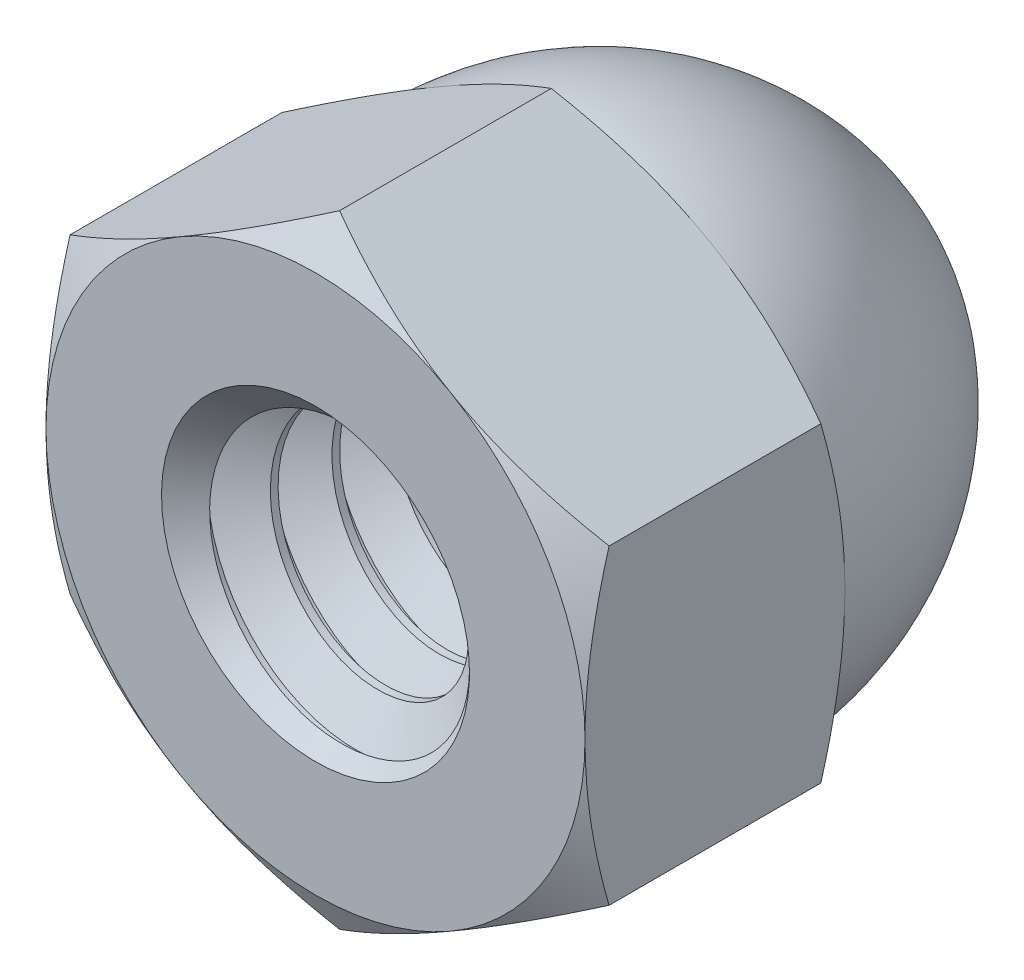
SolidWorks part; units mm, degrees
ref_plane "Front Plane" through (0, 0, 0) normal (0, 0, 1) x (1, 0, 0)
ref_plane "Top Plane" through (0, 0, 0) normal (0, 1, 0) x (1, 0, 0)
ref_plane "Right Plane" through (0, 0, 0) normal (1, 0, 0) x (0, 0, -1)
sketch "Sketch1" plane through (0, 0, 0) normal (0, 0, 1) x (1, 0, 0)
  line L1 (0, 6.4158) -> (-5.5563, 3.2079)
  line L2 (-5.5563, 3.2079) -> (-5.5563, -3.2079)
  line L3 (-5.5563, -3.2079) -> (0, -6.4158)
  line L4 (0, -6.4158) -> (5.5562, -3.2079)
  line L5 (5.5562, -3.2079) -> (5.5562, 3.2079)
  line L6 (5.5562, 3.2079) -> (0, 6.4158)
  circle A0 centre (0, 0) radius 5.5563 construction
  dimension "Hex" = 11.1125
extrude "Extrude1" add sketch "Sketch1" against normal blind 5.3578
sketch "Sketch2" plane through (0, 0, 0) normal (0, 0, 1) x (1, 0, 0)
  circle A0 centre (0, 0) radius 5.5563 construction
  circle A1 centre (0, 0) radius 5.5563
extrude "Cut-Extrude1" cut sketch "Sketch2" against normal through all draft 60 flip side to cut
sketch "Sketch3" plane through (0, 0, -5.3578) normal (0, 0, -1) x (-1, 0, 0)
  circle A1 centre (0, 0) radius 5.5563
  circle A2 centre (0, 0) radius 5.5563
  dimension "D1" = 0
extrude "Cut-Extrude2" cut sketch "Sketch3" against normal through all draft 60 flip side to cut
sketch "Sketch14" plane through (0, 0, 0) normal (1, 0, 0) x (0, 0, -1)
  line L0 (5.3578, 5.5563) -> (5.3578, 0)
  line L1 (5.3578, 0) -> (11.9062, 0)
  line L2 (5.3578, 0) -> (5.3578, 4.8119) construction
  line L3 (5.3578, 5.5563) -> (12.6759, 5.5563) construction
  line L6 (0, 0) -> (5.3578, 0) construction
  arc A0 (5.3578, 5.5563) -> (11.9062, 0) centre (5.3578, -1.0808) cw
  dimension "overall length" = 11.9062
revolve "Revolve1" add sketch "Sketch14" angle 360 about L6
sketch "Sketch4" plane through (0, 0, 0) normal (0, 0, 1) x (1, 0, 0)
  circle A0 centre (0, 0) radius 3.175
  dimension "Thread Dia" = 6.35
extrude "Cut-Extrude3" cut sketch "Sketch4" against normal blind 6.35
sketch "Sketch5" plane through (0, 0, 0) normal (0, 0, 1) x (1, 0, 0)
  circle A0 centre (0, 0) radius 3.175 construction
  circle A1 centre (0, 0) radius 3.175
sketch "Sketch15" plane through (0, 0, -6.35) normal (0, 0, 1) x (1, 0, 0)
  circle A0 centre (0, 0) radius 3.175 construction
  circle A1 centre (0, 0) radius 3.175
curve "Helix/Spiral2" pitch 1.27 height 9.525 turns 7.5 parameters "pitch"=1.27
sketch "Sketch18" plane through (0, 0, 0) normal (0, 0, 1) x (1, 0, 0)
  circle A0 centre (0, 0) radius 3.175 construction
  circle A1 centre (0, 0) radius 3.175
sketch "Sketch16" plane through (0, 0, 0) normal (1, 0, 0) x (0, 0, -1)
  line L0 (6.35, 3.175) -> (7.4613, 3.175)
  line L1 (7.4613, 3.175) -> (6.985, 2.3501)
  line L2 (6.985, 2.3501) -> (6.8263, 2.3501)
  line L3 (6.8263, 2.3501) -> (6.35, 3.175)
  line L4 (6.9056, 2.3501) -> (6.9056, 3.175) construction
  line L5 (6.5881, 2.7626) -> (7.2231, 2.7626) construction
  line L6 (6.35, 3.175) -> (6.35, -3.175) construction
  dimension "D1" = 60
  dimension "D2" = 0.1588
  dimension "D3" = 0.635
sweep "Sweep1" add profiles "Sketch16" path "Helix/Spiral2"
sketch "Sketch17" plane through (0, 0, 0) normal (0, 0, 1) x (1, 0, 0)
  line L6 (0, 6.4158) -> (-5.5563, 3.2079)
  line L7 (-5.5563, 3.2079) -> (-5.5563, -3.2079)
  line L8 (-5.5563, -3.2079) -> (0, -6.4158)
  line L9 (0, -6.4158) -> (5.5562, -3.2079)
  line L10 (5.5562, -3.2079) -> (5.5562, 3.2079)
  line L11 (5.5562, 3.2079) -> (0, 6.4158)
  line L12 (0, 6.4158) -> (-5.5563, 3.2079)
  line L13 (-5.5563, 3.2079) -> (-5.5563, -3.2079)
  line L14 (-5.5563, -3.2079) -> (0, -6.4158)
  line L15 (0, -6.4158) -> (5.5562, -3.2079)
  line L16 (5.5562, -3.2079) -> (5.5562, 3.2079)
  line L17 (5.5562, 3.2079) -> (0, 6.4158)
  dimension "D1" = 0
extrude "Cut-Extrude8" cut sketch "Sketch17" along normal through all
extrude "Cut-Extrude9" cut sketch "Sketch18" against normal through all draft 45
sketch "Sketch20" plane through (0, 0, 0) normal (1, 0, 0) x (0, 0, -1)
  line L0 (6.985, 3.175) -> (8.8181, 0)
  line L1 (6.35, 3.175) -> (6.985, 3.175)
  line L2 (6.35, 3.175) -> (6.35, 0)
  line L3 (6.35, 3.175) -> (7.4613, 3.175) construction
  line L4 (6.35, 3.175) -> (6.35, -3.175) construction
  line L5 (6.35, 0) -> (8.8181, 0)
  line L6 (0, 0) -> (-3.6507, 0) construction
  dimension "D1" = 0.635
  dimension "D2" = 60
revolve "Cut-Revolve1" cut sketch "Sketch20" angle 360 about L6
equation "\"D2@Sketch16\" = \"pitch@Helix/Spiral2\"*.125"
equation "\"D3@Sketch16\" = \"pitch@Helix/Spiral2\"*.50"
equation "\"D1@Sketch20\" = \"pitch@Helix/Spiral2\"/2"
equation "\"D3@Helix/Spiral2\" = \"Thread Depth@Cut-Extrude3\"+.125"
equation "\"Nut Height@Extrude1\" = \"overall length@Sketch14\"*.45"
